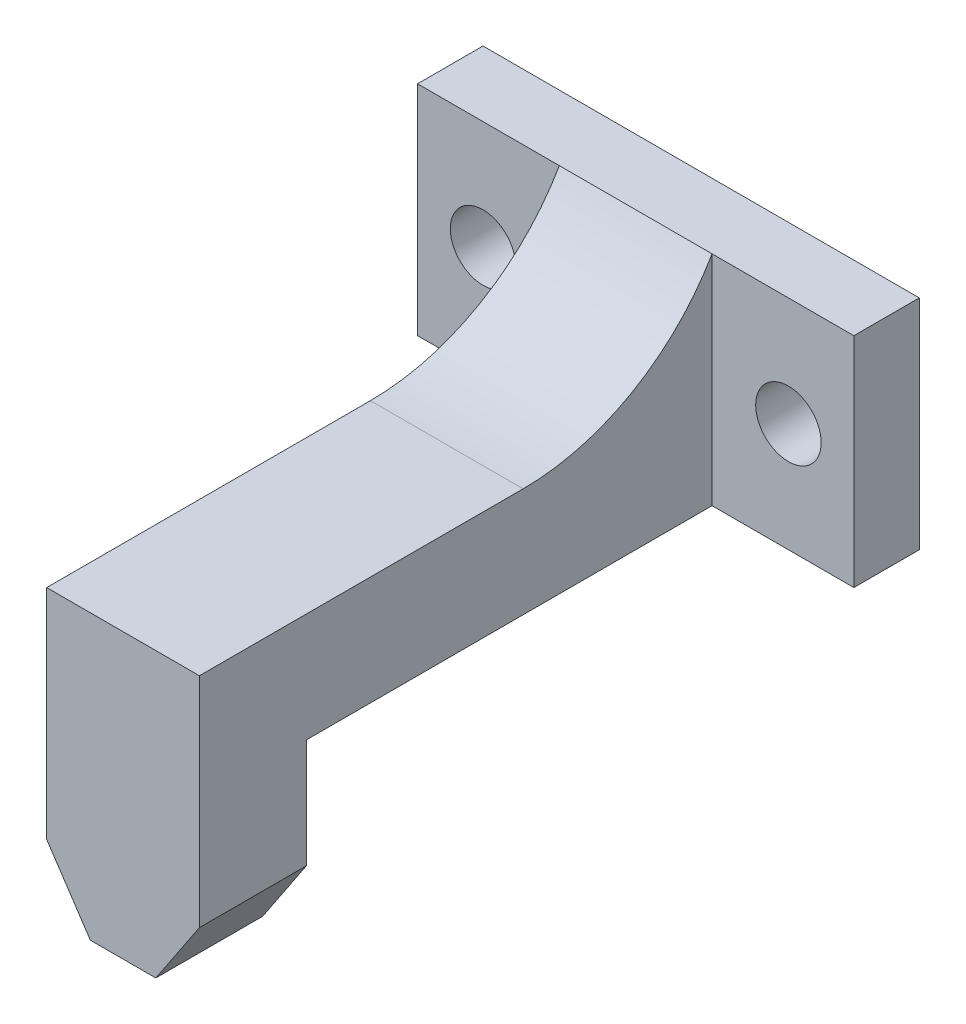
SolidWorks part; units mm, degrees
material "6061 合金"
ref_plane "前视基准面" through (0, 0, 0) normal (0, 0, 1) x (1, 0, 0)
ref_plane "上视基准面" through (0, 0, 0) normal (0, 1, 0) x (1, 0, 0)
ref_plane "右视基准面" through (0, 0, 0) normal (1, 0, 0) x (0, 0, -1)
sketch "草图1" plane through (0, 0, 0) normal (0, 1, 0) x (1, 0, 0)
  line L1 (-3.5, 2.5) -> (3.5, 2.5)
  line L2 (-3.5, 2.5) -> (-3.5, -2.5)
  line L3 (-3.5, -2.5) -> (3.5, -2.5)
  line L4 (3.5, 2.5) -> (3.5, -2.5)
  line L5 (-3.5, 2.5) -> (3.5, -2.5) construction
  line L6 (-3.5, -2.5) -> (3.5, 2.5) construction
  point P0 (0, 0)
  dimension "D1" = 5
  dimension "D2" = 7
extrude "凸台-拉伸1" add sketch "草图1" along normal blind 13
sketch "草图2" plane through (0, 0, -2.5) normal (0, 0, -1) x (-1, 0, 0)
  line L1 (-3.5, 13) -> (3.5, 13)
  line L2 (-3.5, 13) -> (-3.5, 8)
  line L3 (-3.5, 8) -> (3.5, 8)
  line L4 (3.5, 13) -> (3.5, 8)
  point P4 (0, 8)
  dimension "D1" = 5
  dimension "D2" = 7
extrude "凸台-拉伸2" add sketch "草图2" along normal blind 18.5
sketch "草图4" plane through (0, 0, -21) normal (0, 0, -1) x (-1, 0, 0)
  line L0 (0, 8) -> (-10, 8) construction
  line L1 (-3.5, 8) -> (3.5, 8) construction
  line L3 (-10, 8) -> (10, 8)
  line L4 (-10, 8) -> (-10, 18)
  line L5 (-10, 18) -> (10, 18)
  line L6 (10, 8) -> (10, 18)
  dimension "D1" = 10
  dimension "D2" = 10
  dimension "D3" = 20
extrude "凸台-拉伸3" add sketch "草图4" along normal blind 3
sketch "草图5" plane through (0, 0, -24) normal (0, 0, -1) x (-1, 0, 0)
  line L0 (-10, 13) -> (-7, 13) construction
  line L1 (-10, 18) -> (-10, 8) construction
  line L2 (10, 13) -> (7, 13) construction
  line L3 (10, 8) -> (10, 18) construction
  circle A0 centre (-7, 13) radius 1.5
  circle A1 centre (7, 13) radius 1.5
  dimension "D3" = 3
  dimension "D4" = 3
  dimension "D1" = 3
  dimension "D2" = 3
extrude "切除-拉伸1" cut sketch "草图5" against normal through all
fillet "圆角1" radius 10 1 edges at (0, 13, -21)
sketch "草图6" plane through (0, 0, -2.5) normal (0, 0, -1) x (-1, 0, 0)
  line L0 (3.5, 8) -> (3.5, 0) construction
  line L1 (-3.5, 0) -> (3.5, 0)
  line L2 (-3.5, 0) -> (-3.5, 8)
  line L3 (-3.5, 8) -> (3.5, 8)
  line L4 (3.5, 0) -> (3.5, 8)
extrude "切除-拉伸2" cut sketch "草图6" against normal blind 0.1
chamfer "倒角3" distance 2 distance2 3 2 edges at (-3.5, 0, 0.05) (3.5, 0, 0.05) first distance on face at (0, 0, 0.05)
